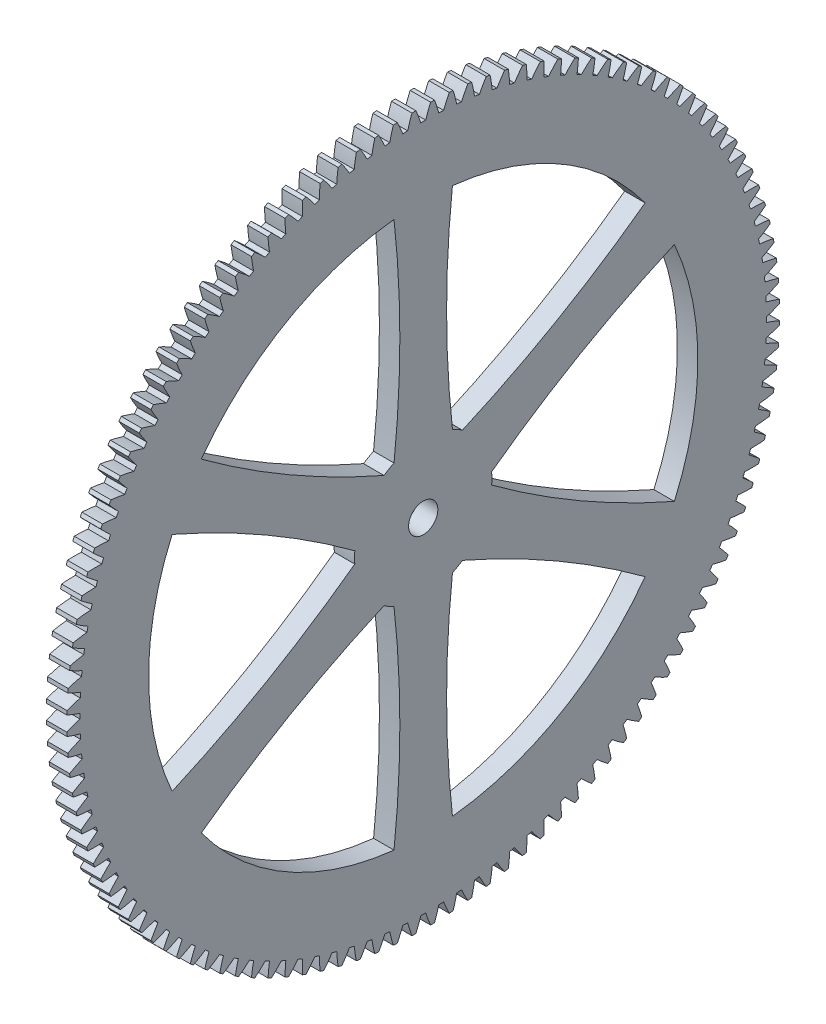
SolidWorks part; units mm, degrees
material "Cedar"
ref_plane "Plane1" through (0, 0, 0) normal (0, 0, 1) x (1, 0, 0)
ref_plane "Plane2" through (0, 0, 0) normal (0, 1, 0) x (1, 0, 0)
ref_plane "Plane3" through (0, 0, 0) normal (1, 0, 0) x (0, 0, -1)
sketch "HoldingSke" plane through (0, 0, 0) normal (0, 1, 0) x (1, 0, 0)
  line L0 (0, 0) -> (-254, -439.9409)
  line L1 (-15, 0) -> (100, 0) construction
  line L2 (0, 0) -> (-2.1039, 2.3779)
  line L3 (0, 0) -> (-11.863, 4.5341)
  line L4 (0, 0) -> (-4.318, 7.479)
  line L5 (0, 0) -> (-47.5972, -17.7524)
  line L6 (0, 0) -> (-3.6847, -2.4861)
  line L7 (-2.1039, 2.3779) -> (8.8308, 51.9871)
  line L8 (-76.2, 54.61) -> (-69.596, 54.61)
  line L9 (-71.009, 38.7566) -> (-53.1078, 45.2721)
  line L10 (-76.2, 71.12) -> (104.1128, 71.12)
  line L11 (0, 0) -> (-4.445, 0)
  line L12 (-76.2, 101.6) -> (-76.1492, 101.6)
  line L13 (24.9733, 27.94) -> (52.9518, 28.4284)
  line L14 (24.9733, 27.94) -> (25.0241, 27.9398)
  line L15 (24.9733, 27.94) -> (100.4021, 29.52)
  circle A0 centre (0, 0) radius 3.175
  circle A1 centre (0, 0) radius 38.1
  circle A2 centre (0, 0) radius 38.1
  circle A3 centre (0, 0) radius 3.175
  dimension "MHD" = 76.2
  dimension "Hub_dia" = 76.2
  dimension "Bore" = 6.35
  dimension "MBD" = 6.35
  dimension "Num_teeth" = 120
  dimension "Pitch_radius" = 180.3128
  dimension "Pitch" = 508
  dimension "Width" = 4.445
  dimension "Overall_len" = 50.8
  dimension "Show_teeth" = 120
  dimension "Thickness" = 4.445
  dimension "OAL" = 50.8001
  dimension "T_dim" = 6.604
  dimension "Ap" = 20
  dimension "H" = 19.05
  dimension "Backlash" = 0.0508
  dimension "Addendum_fac" = 1
  dimension "Dedendum_fac" = 1.2
  dimension "Clearance_fac" = 0.2
  dimension "Dedendum_add" = 0.0508
sketch "BasProSke" plane through (0, 0, 0) normal (0, 1, 0) x (1, 0, 0)
  line L0 (-10, 0) -> (60, 0) construction
  line L1 (0, 0) -> (0, 77.47)
  line L2 (0, 0) -> (4.445, 0)
  line L3 (4.445, 0) -> (4.445, 77.47)
  line L4 (4.445, 77.47) -> (0, 77.47)
  dimension "Diameter" = 154.94
  dimension "Thickness" = 4.445
revolve "Base-Revolve" add sketch "BasProSke" angle 360 about L0
sketch "TooCutSke" plane through (0, 0, 0) normal (1, 0, 0) x (0, 0, -1)
  line L1 (0, 0) -> (0, 107) construction
  line L2 (0, 0) -> (-1.0863, 76.1923) construction
  line L3 (0, 0) -> (-3.9891, 152.3369) construction
  line L4 (-1.0863, 76.1923) -> (-1.9945, 76.1685) construction
  arc A0 (0.5305, 74.6233) -> (-0.5305, 74.6233) centre (0, 0) ccw
  arc A1 (1.616, 77.4785) -> (-1.616, 77.4785) centre (0, 0) ccw
  circle A2 centre (0, 0) radius 76.2 construction
  circle A3 centre (0, 0) radius 71.6046 construction
  arc A4 (-0.5305, 74.6233) -> (-1.616, 77.4785) centre (-29.5279, 65.2328) ccw
  arc A5 (1.616, 77.4785) -> (0.5305, 74.6233) centre (29.5279, 65.2328) ccw
  dimension "Root_dia" = 149.2504
  dimension "Overcut_dia" = 154.9908
  dimension "Pitch_dia" = 152.4
  dimension "Base_dia" = 143.2092
  dimension "Flank_rad" = 30.48
  dimension "Half_ang" = 1.5
  dimension "Half_CT" = 0.9085
extrude "ToothCut" cut sketch "TooCutSke" along normal through all
fillet "Breaks" [suppressed] radius 0.0254 tangent propagation no
fillet "RootFillets" [suppressed] radius 0.3048
pattern_circular "TeethCuts" count 120 every 3 about axis through (-10, 0, 0) along (1, 0, 0) of "ToothCut", "RootFillets", "Breaks"
sketch "HubNeaOneSke" plane through (0, 0, 0) normal (-1, 0, 0) x (0, 0, 1)
  circle A0 centre (0, 0) radius 38.1
  dimension "Diameter" = 76.2
extrude "HubNearOne" [suppressed] add sketch "HubNeaOneSke" along normal blind 46.3551
sketch "HubNeaBotSke" plane through (0, 0, 0) normal (-1, 0, 0) x (0, 0, 1)
  circle A0 centre (0, 0) radius 38.1
  dimension "Diameter" = 76.2
extrude "HubNearBoth" [suppressed] add sketch "HubNeaBotSke" along normal blind 23.1775
ref_plane "FarPln" through (4.445, 0, 0) normal (1, 0, 0) x (0, 0, -1)
sketch "HubFarSke" plane through (4.445, 0, 0) normal (1, 0, 0) x (0, 0, -1)
  circle A0 centre (0, 0) radius 38.1
  dimension "Diameter" = 76.2
extrude "HubFar" [suppressed] add sketch "HubFarSke" along normal blind 23.1775
sketch "BorSke" plane through (0, 0, 0) normal (1, 0, 0) x (0, 0, -1)
  circle A0 centre (0, 0) radius 3.175
  dimension "Diameter" = 6.35
extrude "Bore" cut sketch "BorSke" along normal mid plane 101.6001
sketch "KeySke" plane through (0, 0, 0) normal (1, 0, 0) x (0, 0, -1)
  line L0 (-0.127, 0) -> (-0.127, 3.429)
  line L1 (-0.127, 3.429) -> (0.127, 3.429)
  line L2 (0.127, 3.429) -> (0.127, 0)
  line L3 (0, 0) -> (0, 34) construction
  line L4 (-0.127, 0) -> (0.127, 0)
  dimension "Offset" = 3.429
  dimension "Width" = 0.254
extrude "Keyway" [suppressed] cut sketch "KeySke" along normal mid plane 101.6001
pattern_circular "Keyway2" [suppressed] count 2 every 90 about axis through (-10, 0, 0) along (1, 0, 0)
sketch "Sketch1" plane through (0, 0, 0) normal (-1, 0, 0) x (0, 0, 1)
  circle A0 centre (0, 0) radius 76.2
  dimension "D1" = 152.4
sketch "Sketch2" plane through (0, 0, 0) normal (-1, 0, 0) x (0, 0, 1)
  line L0 (-6.35, 59.3615) -> (-6.35, 13.5068)
  line L1 (-6.35, 59.3615) -> (6.35, 59.3615)
  line L2 (-6.35, 13.5068) -> (6.35, 13.5068)
  line L3 (6.35, 59.3615) -> (6.35, 13.5068)
  circle A0 centre (0, 0) radius 14.925
  circle A1 centre (0, 0) radius 59.7002
  arc A2 (-6.35, 13.5068) -> (-6.35, 59.3615) centre (-212.6688, 36.4342) ccw
  arc A3 (6.35, 13.5068) -> (6.35, 59.3615) centre (212.6688, 36.4342) cw
  arc A4 (8.5223, 12.2527) -> (48.2336, 35.18) centre (-74.7815, 202.3936) ccw
  arc A5 (14.8723, 1.2542) -> (54.5836, 24.1815) centre (137.8873, -165.9595) cw
  arc A6 (14.8723, -1.2542) -> (54.5836, -24.1815) centre (137.8873, 165.9595) ccw
  arc A7 (8.5223, -12.2527) -> (48.2336, -35.18) centre (-74.7815, -202.3936) cw
  arc A8 (6.35, -13.5068) -> (6.35, -59.3615) centre (212.6688, -36.4342) ccw
  arc A9 (-6.35, -13.5068) -> (-6.35, -59.3615) centre (-212.6688, -36.4342) cw
  arc A10 (-8.5223, -12.2527) -> (-48.2336, -35.18) centre (74.7815, -202.3936) ccw
  arc A11 (-14.8723, -1.2542) -> (-54.5836, -24.1815) centre (-137.8873, 165.9595) cw
  arc A12 (-14.8723, 1.2542) -> (-54.5836, 24.1815) centre (-137.8873, -165.9595) ccw
  arc A13 (-8.5223, 12.2527) -> (-48.2336, 35.18) centre (74.7815, 202.3936) cw
  point P8 (-5.08, 36.4342)
  point P9 (5.08, 36.4342)
  point P45 (0, 0)
  dimension "D1" = 119.4003
  dimension "D2" = 29.8501
  dimension "D4" = 10.16
  dimension "D3" = 12.7
  dimension "D5" = 6
extrude "Cut-Extrude1" cut sketch "Sketch2" against normal through all contours A13 A0 L0 A1 | A0 A12 A1 A11 | A0 A10 A1 A9 | A0 A8 A1 A7 | A0 A6 A1 A5 | A0 A4 A1 L3 | A3 L3 | L0 A2 region at (0, 36.4342, -5.8419) region at (0, 36.752, -21.7045) region at (0, 36.752, 21.7045) region at (0, 36.4342, 5.8419) region at (0, 0, -42.4262) region at (0, 0, 42.4262) region at (0, -36.7422, -21.2131) region at (0, -36.7422, 21.2131)
equation "' \"Pitch@HoldingSke\" = 4"
equation "' \"Num_teeth@HoldingSke\" = 12"
equation "' \"Ap@HoldingSke\" =  20"
equation "' \"Width@HoldingSke\" = 0.5"
equation "' \"Hub_dia@HoldingSke\"= 1"
equation "' \"Overall_len@HoldingSke\" = 1.0"
equation "' \"Bore@HoldingSke\" = 0.75"
equation "' \"T_dim@HoldingSke\" = 0.85"
equation "' \"Width@KeySke\" = 0.25"
equation "' \"Show_teeth@HoldingSke\" = 13"
equation "' \"Backlash@HoldingSke\" = 0.009"
equation "' \"Addendum_fac@HoldingSke\" = 1.0"
equation "' \"Dedendum_fac@HoldingSke\" = 1.25"
equation "' \"Dedendum_add@HoldingSke\" = 0.00005"
equation "' \"Clearance_fac@HoldingSke\" = 0.25"
equation "' \"Pitch@HoldingSke\" = 0.5"
equation "' \"Num_teeth@HoldingSke\" = 23"
equation "' \"Show_teeth@HoldingSke\" = 23"
equation "' \"Backlash@HoldingSke\" = 0.0375"
equation "\"Overcut_dia@TooCutSke\" = (\"Num_teeth@HoldingSke\" + 2 * \"Addendum_fac@HoldingSke\") / \"Pitch@HoldingSke\" + 0.002"
equation "\"Pitch_dia@TooCutSke\" = \"Num_teeth@HoldingSke\" / \"Pitch@HoldingSke\""
equation "\"Base_dia@TooCutSke\" = \"Num_teeth@HoldingSke\" / \"Pitch@HoldingSke\" * cos((\"Ap@HoldingSke\"  * 3.14159265 / 180))"
equation "\"Root_dia@TooCutSke\" = (\"Num_teeth@HoldingSke\" + 2) / \"Pitch@HoldingSke\" - 2 * (\"Addendum_fac@HoldingSke\" + \"Dedendum_fac@HoldingSke\") / \"Pitch@HoldingSke\" - \"Dedendum_add@HoldingSke\" * 2"
equation "\"Half_ang@TooCutSke\" = 180 / \"Num_teeth@HoldingSke\""
equation "\"Half_CT@TooCutSke\" = \"Num_teeth@HoldingSke\" / \"Pitch@HoldingSke\" * sin((3.14159265 / 2 / \"Num_teeth@HoldingSke\")) / 2 - 7 * \"Backlash@HoldingSke\" / 4"
equation "\"Flank_rad@TooCutSke\" = \"Num_teeth@HoldingSke\" / \"Pitch@HoldingSke\" / 5"
equation "\"Radius@RootFillets\" = \"Clearance_fac@HoldingSke\" / \"Pitch@HoldingSke\" + \"Dedendum_add@HoldingSke\""
equation "\"Break_rad@Breaks\" = 0.02 / \"Pitch@HoldingSke\""
equation "\"Thickness@HoldingSke\" = \"Width@HoldingSke\""
equation "\"OAL@HoldingSke\" = \"Thickness@HoldingSke\""
equation "\"MHD@HoldingSke\" = (\"Num_teeth@HoldingSke\" + 2) / \"Pitch@HoldingSke\" - 2 * (\"Addendum_fac@HoldingSke\" + \"Dedendum_fac@HoldingSke\")  / \"Pitch@HoldingSke\" - \"Dedendum_add@HoldingSke\" * 2"
equation "\"MBD@HoldingSke\" = (\"Num_teeth@HoldingSke\" + 2) / \"Pitch@HoldingSke\" - 2 * (\"Addendum_fac@HoldingSke\" + \"Dedendum_fac@HoldingSke\")  / \"Pitch@HoldingSke\" - \"Dedendum_add@HoldingSke\" * 2 - 0.002"
equation "\"MHD@HoldingSke\" = ((sgn( \"MHD@HoldingSke\" - \"Hub_dia@HoldingSke\" )-1)*( \"MHD@HoldingSke\" - \"Hub_dia@HoldingSke\" ))/-2+ \"Hub_dia@HoldingSke\""
equation "\"MBD@HoldingSke\" = ((sgn( \"MBD@HoldingSke\" - \"Bore@HoldingSke\" )-1)*( \"MBD@HoldingSke\" - \"Bore@HoldingSke\" ))/-2+ \"Bore@HoldingSke\""
equation "\"OAL@HoldingSke\" = ((sgn( \"OAL@HoldingSke\" - \"Overall_len@HoldingSke\" )+1)*( \"OAL@HoldingSke\" - \"Overall_len@HoldingSke\" ))/2 + \"Overall_len@HoldingSke\" + 0.000002"
equation "\"Num_teeth@TeethCuts\" = int( \"Show_teeth@HoldingSke\" ) + 1"
equation "\"Num_teeth@TeethCuts\" = ((sgn( \"Num_teeth@TeethCuts\" - \"Num_teeth@HoldingSke\" )-1)*( \"Num_teeth@TeethCuts\" - \"Num_teeth@HoldingSke\" ))/-2+ \"Num_teeth@HoldingSke\""
equation "\"Num_teeth@TeethCuts\" = ((sgn( \"Num_teeth@TeethCuts\" - 2.0)+1)*( \"Num_teeth@TeethCuts\" - 2.0))/2 +2.0"
equation "\"Angle@TeethCuts\" = 360.0 / \"Num_teeth@HoldingSke\""
equation "\"Diameter@BasProSke\" = (\"Num_teeth@HoldingSke\" + 2 * \"Addendum_fac@HoldingSke\") / \"Pitch@HoldingSke\""
equation "\"Thickness@BasProSke\"  = \"Thickness@HoldingSke\""
equation "' \"Fillet_rad@BasProSke\" =  \"Thickness@HoldingSke\" * 0.05"
equation "\"MHD@HoldingSke\" = ((sgn( \"MHD@HoldingSke\" - \"Root_dia@TooCutSke\" )-1)*( \"MHD@HoldingSke\" - \"Root_dia@TooCutSke\" ))/-2+ \"Root_dia@TooCutSke\""
equation "\"Diameter@HubNeaOneSke\" = \"MHD@HoldingSke\""
equation "\"Length@HubNearOne\" = \"OAL@HoldingSke\" - \"Thickness@BasProSke\""
equation "\"Diameter@HubNeaBotSke\" = \"MHD@HoldingSke\""
equation "\"Length@HubNearBoth\" = ( \"OAL@HoldingSke\" - \"Thickness@BasProSke\" ) / 2.0"
equation "\"Thickness@FarPln\" = \"Thickness@BasProSke\""
equation "\"Diameter@HubFarSke\" = \"MHD@HoldingSke\""
equation "\"Length@HubFar\" = ( \"OAL@HoldingSke\" - \"Thickness@BasProSke\" ) / 2.0"
equation "\"Diameter@BorSke\" = \"MBD@HoldingSke\""
equation "\"D1@Bore\" = \"OAL@HoldingSke\" * 2.0"
equation "\"D1@Keyway\" = \"OAL@HoldingSke\" * 2.0"
equation "\"Offset@KeySke\" = \"T_dim@HoldingSke\" - \"MBD@HoldingSke\" / 2.0"
